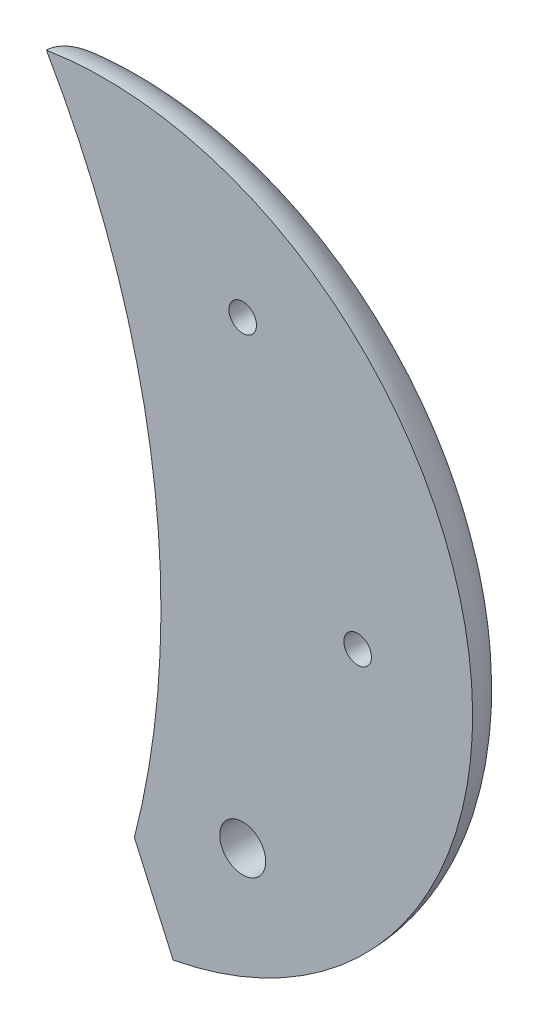
SolidWorks part; units mm, degrees
ref_plane "Front Plane" through (0, 0, 0) normal (0, 0, 1) x (1, 0, 0)
ref_plane "Top Plane" through (0, 0, 0) normal (0, 1, 0) x (1, 0, 0)
ref_plane "Right Plane" through (0, 0, 0) normal (1, 0, 0) x (0, 0, -1)
sketch "Sketch1" plane through (0, 0, 0) normal (0, 0, 1) x (1, 0, 0)
  line L2 (0, 14.4967) -> (0, 0) construction
  circle A0 centre (0, 0) radius 40
  arc A1 (-6.3493, 39.4929) -> (0, -40) centre (-86.5413, -6.9123) cw
  dimension "D1" = 80
  dimension "D3" = 14.4967
extrude "Boss-Extrude1" add sketch "Sketch1" along normal blind 5 contours A0 A1 region at (18.3564, 1.4662, 0)
sketch "Sketch2" plane through (0, 0, 5) normal (0, 0, 1) x (1, 0, 0)
  line L0 (0, 0) -> (15, 0) construction
  line L1 (15, 0) -> (15, -25) construction
  line L2 (15, 0) -> (27.5, 0) construction
  line L3 (0, 0) -> (0, 25) construction
  line L4 (0, 25) -> (15, 25) construction
  circle A0 centre (15, -25) radius 2.5
  circle A1 centre (27.5, 0) radius 1.5
  circle A3 centre (15, 25) radius 1.5
  dimension "D1" = 5
  dimension "D5" = 3
  dimension "D6" = 3
  dimension "D2" = 15
  dimension "D3" = 25
  dimension "D4" = 12.5
  dimension "D7" = 25
  dimension "D8" = 15
extrude "Cut-Extrude1" cut sketch "Sketch2" against normal blind 10
sketch "Sketch4" plane through (0, 0, 5) normal (0, 0, 1) x (1, 0, 0)
  line L0 (0, 0) -> (17.2942, 17.2942) construction
  line L1 (0, 0) -> (17.2942, -17.2942) construction
  line L2 (0, 0) -> (18.5, 0) construction
  line L3 (0, 0) -> (-5.7931, 0) construction
  arc A0 (17.2942, 17.2942) -> (17.2942, -17.2942) centre (-106.1241, 0) cw construction
  arc A14 (19.77, -17.6411) -> (19.77, 17.6411) centre (-106.1241, 0) ccw
  arc A15 (14.8184, -16.9473) -> (14.8184, 16.9473) centre (-106.1241, 0) ccw
  arc A16 (14.8184, -16.9473) -> (19.77, -17.6411) centre (17.2942, -17.2942) ccw
  arc A17 (19.77, 17.6411) -> (14.8184, 16.9473) centre (17.2942, 17.2942) ccw
  point P4 (18.5, 0)
  dimension "D1" = 2.5
  dimension "D2" = 18.5
  dimension "D4" = 180
  dimension "D5" = 45
  dimension "D6" = 45
extrude "Cut-Extrude2" [suppressed] cut sketch "Sketch4" against normal blind 10
chamfer "Chamfer1" distance 10 angle 45 1 edges at (0, -40, 2.5) first distance on face at (1.3204, 0.1055, 2.5)
fillet "Fillet2" radius 5 3 edges at (5.3266, -34.5879, 0) (5.2404, 5.749, 0) (39.4018, 6.8921, 0)
